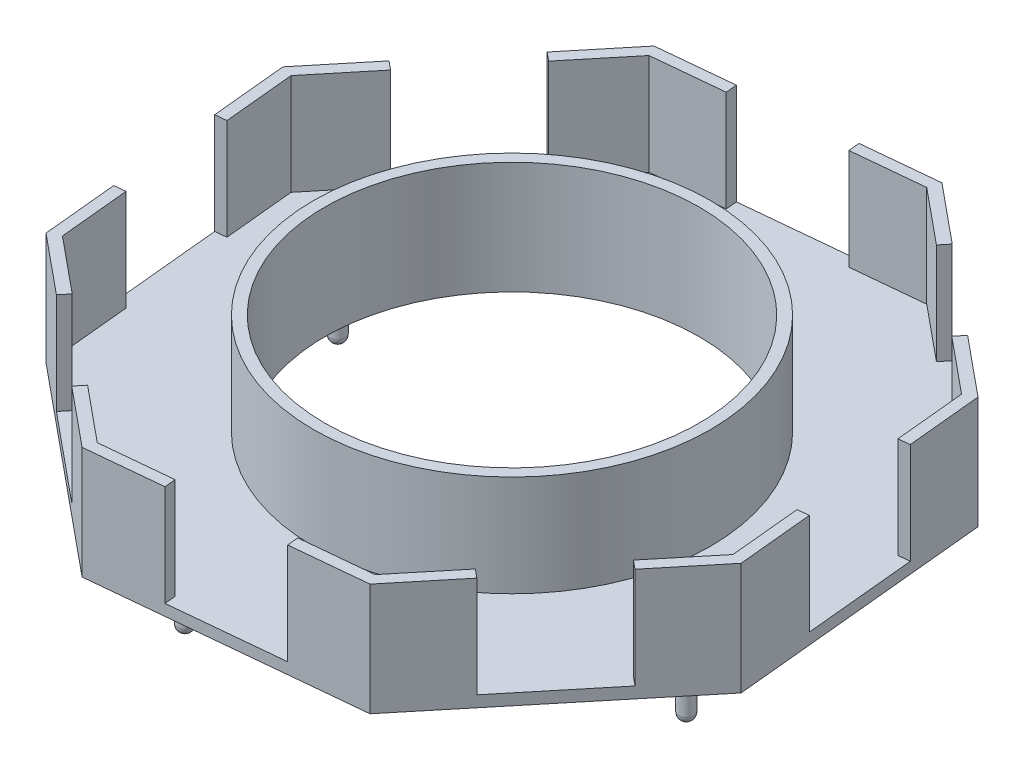
SolidWorks part; units mm, degrees
ref_plane "Front Plane" through (0, 0, 0) normal (0, 0, 1) x (1, 0, 0)
ref_plane "Top Plane" through (0, 0, 0) normal (0, 1, 0) x (1, 0, 0)
ref_plane "Right Plane" through (0, 0, 0) normal (1, 0, 0) x (0, 0, -1)
sketch "Sketch1" plane through (0, 0, 0) normal (0, 1, 0) x (1, 0, 0)
  line L0 (-43.2676, 81.1944) -> (-88.0079, 26.8183)
  line L1 (-81.1944, -43.2676) -> (-26.8183, -88.0079)
  line L2 (-26.8183, -88.0079) -> (43.2676, -81.1944)
  line L3 (43.2676, -81.1944) -> (88.0079, -26.8183)
  line L4 (88.0079, -26.8183) -> (81.1944, 43.2676)
  line L5 (81.1944, 43.2676) -> (26.8183, 88.0079)
  line L6 (26.8183, 88.0079) -> (-43.2676, 81.1944)
  line L7 (-88.0079, 26.8183) -> (-81.1944, -43.2676)
  circle A0 centre (0, 0) radius 50
  circle A1 centre (0, 0) radius 85 construction
extrude "Boss-Extrude1" add sketch "Sketch1" along normal blind 30
sketch "Sketch2" plane through (0, 0, 0) normal (0, -1, 0) x (-1, 0, 0)
  circle A0 centre (66.9601, 20.4045) radius 2
  circle A1 centre (20.4045, -66.9601) radius 2
  circle A2 centre (-66.9601, -20.4045) radius 2
  circle A3 centre (-20.4045, 66.9601) radius 2
  point P12 (0, 0)
  dimension "D1" = 4
extrude "Boss-Extrude2" add sketch "Sketch2" along normal blind 20
fillet "Fillet1" radius 2 8 edges at (-66.9601, 0, -18.4045) (-66.9601, -20, -22.4045) (20.4045, 0, -64.9601) (20.4045, -20, -68.9601) (66.9601, 0, 22.4045) (66.9601, -20, 18.4045) (-20.4045, 0, 68.9601) (-20.4045, -20, 64.9601)
shell "Shell1" thickness 3 removed face at (0, 30, 0)
sketch "Sketch3" plane through (0, 30, 0) normal (0, 1, 0) x (1, 0, 0)
  line L0 (6.6346, 86.0457) -> (6.9249, 83.0598)
  line L1 (26.8183, 88.0079) -> (-43.2676, 81.1944) construction
  line L2 (25.8718, 84.9017) -> (-41.7405, 78.3287) construction
  line L3 (6.9249, 83.0598) -> (-22.9343, 80.157)
  line L4 (-22.9343, 80.157) -> (-23.2246, 83.1429)
  line L5 (-23.2246, 83.1429) -> (6.6346, 86.0457)
  line L6 (63.6288, 53.8355) -> (40.4625, 72.8966)
  line L7 (42.3686, 75.2132) -> (65.5349, 56.1521)
  line L8 (65.5349, 56.1521) -> (63.6288, 53.8355)
  line L9 (40.4625, 72.8966) -> (42.3686, 75.2132)
  line L10 (83.0598, -6.9249) -> (80.157, 22.9343)
  line L11 (83.1429, 23.2246) -> (86.0457, -6.6346)
  line L12 (86.0457, -6.6346) -> (83.0598, -6.9249)
  line L13 (80.157, 22.9343) -> (83.1429, 23.2246)
  line L14 (53.8355, -63.6288) -> (72.8966, -40.4625)
  line L15 (75.2132, -42.3686) -> (56.1521, -65.5349)
  line L16 (56.1521, -65.5349) -> (53.8355, -63.6288)
  line L17 (72.8966, -40.4625) -> (75.2132, -42.3686)
  line L18 (-6.9249, -83.0598) -> (22.9343, -80.157)
  line L19 (23.2246, -83.1429) -> (-6.6346, -86.0457)
  line L20 (-6.6346, -86.0457) -> (-6.9249, -83.0598)
  line L21 (22.9343, -80.157) -> (23.2246, -83.1429)
  line L22 (-63.6288, -53.8355) -> (-40.4625, -72.8966)
  line L23 (-42.3686, -75.2132) -> (-65.5349, -56.1521)
  line L24 (-65.5349, -56.1521) -> (-63.6288, -53.8355)
  line L25 (-40.4625, -72.8966) -> (-42.3686, -75.2132)
  line L26 (-83.0598, 6.9249) -> (-80.157, -22.9343)
  line L27 (-83.1429, -23.2246) -> (-86.0457, 6.6346)
  line L28 (-86.0457, 6.6346) -> (-83.0598, 6.9249)
  line L29 (-80.157, -22.9343) -> (-83.1429, -23.2246)
  line L30 (-53.8355, 63.6288) -> (-72.8966, 40.4625)
  line L31 (-75.2132, 42.3686) -> (-56.1521, 65.5349)
  line L32 (-56.1521, 65.5349) -> (-53.8355, 63.6288)
  line L33 (-72.8966, 40.4625) -> (-75.2132, 42.3686)
  point P6 (-8.295, 84.5943)
  point P39 (0, 0)
  dimension "D1" = 30
  dimension "D2" = 15
  dimension "D3" = 8
extrude "Cut-Extrude1" cut sketch "Sketch3" against normal blind 27
